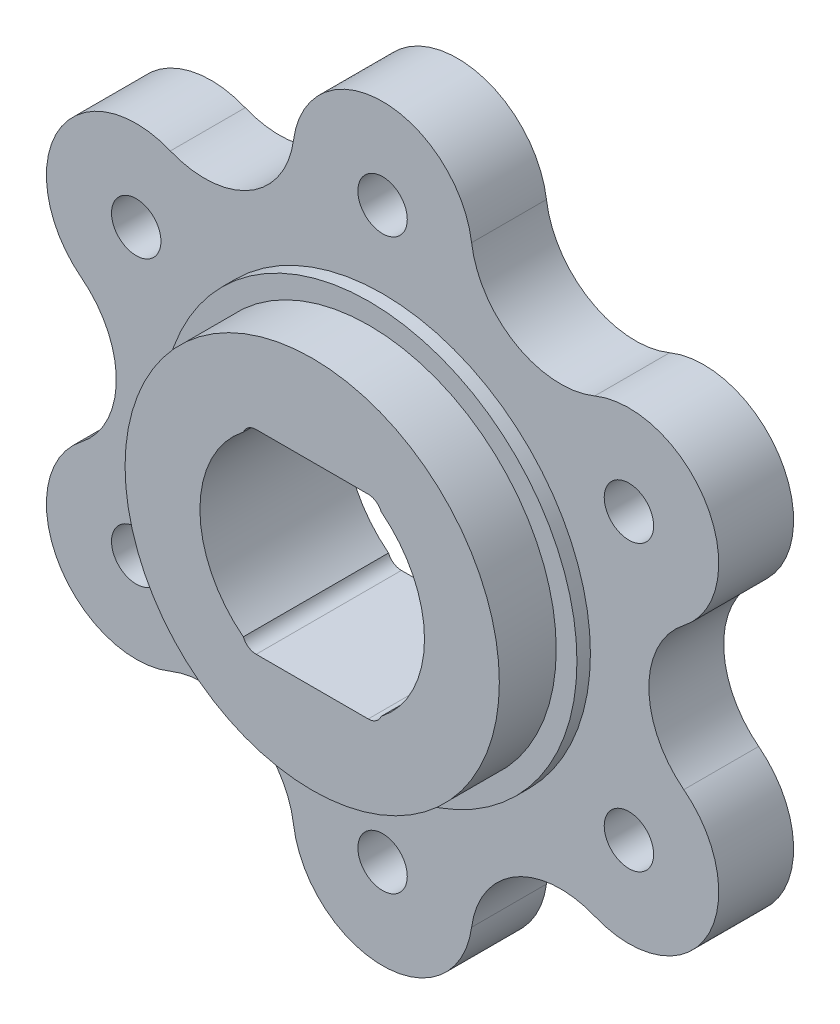
SolidWorks part; units mm, degrees
note: The reader was unsure of these and kept them because the rebuilt part matched: shared geometry of "ｽｹｯﾁ1<3>", "ｽｹｯﾁ1<4>", "ｽｹｯﾁ1<5>".
material "3.1325 (EN-AW 2017A)"
ref_plane "正面" through (0, 0, 0) normal (0, 0, 1) x (1, 0, 0)
ref_plane "平面" through (0, 0, 0) normal (0, 1, 0) x (1, 0, 0)
ref_plane "右側面" through (0, 0, 0) normal (1, 0, 0) x (0, 0, -1)
sketch "ｽｹｯﾁ1" plane through (0, 0, 0) normal (0, 0, 1) x (1, 0, 0)
  line L0 (-3.7417, 6.5) -> (3.7417, 6.5)
  line L1 (3.7417, -6.5) -> (-3.7417, -6.5)
  line L2 (0, 0) -> (0, 19) construction
  arc A0 (-3.7417, 6.5) -> (-3.7417, -6.5) centre (0, 0) ccw
  arc A1 (3.7417, -6.5) -> (3.7417, 6.5) centre (0, 0) ccw
  circle A2 centre (0, 0) radius 12.5
  circle A3 centre (0, 0) radius 13.883
  arc A4 (5.9465, 19.7996) -> (-5.9465, 19.7996) centre (0, 19) ccw
  arc A5 (5.9465, 19.7996) -> (14.1737, 15.0496) centre (11.893, 20.5992) ccw
  arc A6 (20.1202, 4.75) -> (14.1737, 15.0496) centre (16.4545, 9.5) ccw
  arc A7 (20.1202, 4.75) -> (20.1202, -4.75) centre (23.7859, 0) ccw
  arc A8 (14.1737, -15.0496) -> (20.1202, -4.75) centre (16.4545, -9.5) ccw
  arc A9 (14.1737, -15.0496) -> (5.9465, -19.7996) centre (11.893, -20.5992) ccw
  arc A10 (-5.9465, -19.7996) -> (5.9465, -19.7996) centre (0, -19) ccw
  arc A11 (-5.9465, -19.7996) -> (-14.1737, -15.0496) centre (-11.893, -20.5992) ccw
  arc A12 (-20.1202, -4.75) -> (-14.1737, -15.0496) centre (-16.4545, -9.5) ccw
  arc A13 (-20.1202, -4.75) -> (-20.1202, 4.75) centre (-23.7859, 0) ccw
  arc A14 (-14.1737, 15.0496) -> (-20.1202, 4.75) centre (-16.4545, 9.5) ccw
  arc A15 (-14.1737, 15.0496) -> (-5.9465, 19.7996) centre (-11.893, 20.5992) ccw
  circle A16 centre (0, 0) radius 19 construction
  circle A18 centre (0, 0) radius 4
  point P41 (0, 0)
  dimension "D1" = 15
  dimension "D3" = 25
  dimension "D4" = 27.766
  dimension "D5" = 6
  dimension "D6" = 6
  dimension "D7" = 6
  dimension "D8" = 38
  dimension "D9" = 8
  dimension "D2" = 13
extrude "ﾎﾞｽ - 押し出し1" add sketch "ｽｹｯﾁ1" along normal blind 5 contours A5 A6 A7 A8 A9 A10 A11 A12 A13 A14 A15 A4
extrude "ﾎﾞｽ - 押し出し2" add sketch "ｽｹｯﾁ1<3>" along normal blind 5.9 contours A3
sketch "ｽｹｯﾁ1<3>" plane through (0, 0, 0) normal (0, 0, 1) x (1, 0, 0) same geometry as "ｽｹｯﾁ1"
extrude "ﾎﾞｽ - 押し出し3" add sketch "ｽｹｯﾁ1<4>" along normal blind 9.7 contours A2
sketch "ｽｹｯﾁ1<4>" plane through (0, 0, 0) normal (0, 0, 1) x (1, 0, 0) same geometry as "ｽｹｯﾁ1"
extrude "ｶｯﾄ - 押し出し1" cut sketch "ｽｹｯﾁ1<5>" along normal through all contours L0 A1 L1 A0
sketch "ｽｹｯﾁ1<5>" plane through (0, 0, 0) normal (0, 0, 1) x (1, 0, 0) same geometry as "ｽｹｯﾁ1"
hole_wizard "M4x0.7 ねじ穴1" positions "3Dｽｹｯﾁ1" profile "ｽｹｯﾁ2" tap size "M4x0.7" standard "JIS" end condition through all
sketch3d "3Dｽｹｯﾁ1"
  point P0 (0, 19, 0)
  point P2 (16.4545, 9.5, 0)
  point P4 (16.4545, -9.5, 0)
  point P6 (0, -19, 0)
  point P8 (-16.4545, -9.5, 0)
  point P10 (-16.4545, 9.5, 0)
sketch "ｽｹｯﾁ2" plane through (0, 19, 0) normal (1, 0, 0) x (0, 1, 0)
  line L0 (0, 0) -> (0, 9.7)
  line L1 (0, 9.7) -> (1.65, 9.7)
  line L2 (1.65, 9.7) -> (1.65, 0)
  line L5 (1.65, 0) -> (0, 0)
  line L11 (0, -6.35) -> (0, 107.95) construction
  dimension "次ｻｰﾌｪｽまでのねじ下穴ﾄﾞﾘﾙ直径" = 3.3
  dimension "次ｻｰﾌｪｽまでのねじ下穴ﾄﾞﾘﾙの深さ" = 9.7
cosmetic thread "穴のねじ山1" parameters "D2"=4
cosmetic thread "穴のねじ山2" parameters "D2"=4
cosmetic thread "穴のねじ山3" parameters "D2"=4
cosmetic thread "穴のねじ山4" parameters "D2"=4
cosmetic thread "穴のねじ山5" parameters "D2"=4
cosmetic thread "穴のねじ山6" parameters "D2"=4
hole_wizard "M5 穴付きねじ用座ぐり穴1" [suppressed] positions "3Dｽｹｯﾁ2" profile "ｽｹｯﾁ3" counterbore size "M5" standard "JIS"
sketch3d "3Dｽｹｯﾁ2"
  point P0 (0, 0, 9.7)
sketch "ｽｹｯﾁ3" plane through (0, 0, 9.7) normal (1, 0, 0) x (0, -1, 0)
  line L0 (0, 0) -> (0, 9.7)
  line L1 (0, 9.7) -> (2.65, 9.7)
  line L3 (2.65, 9.7) -> (2.65, 5)
  line L4 (2.65, 5) -> (5, 5)
  line L5 (5, 5) -> (5, 0)
  line L7 (5, 0) -> (0, 0)
  line L11 (0, -6.35) -> (0, 107.95) construction
  dimension "通し穴の直径" = 5.3
  dimension "通し穴の深さ" = 9.7
  dimension "座ぐり穴の直径" = 10
  dimension "座ぐり穴の深さ" = 5
hole_wizard "M4 丸皿ねじ用皿穴1" [suppressed] positions "3Dｽｹｯﾁ3" profile "ｽｹｯﾁ4" countersink size "M4" standard "JIS"
sketch3d "3Dｽｹｯﾁ3"
  point P0 (0, 19, 5)
  point P2 (-16.4545, 9.5, 5)
  point P4 (-16.4545, -9.5, 5)
  point P6 (0, -19, 5)
  point P8 (16.4545, -9.5, 5)
  point P10 (16.4545, 9.5, 5)
sketch "ｽｹｯﾁ4" plane through (0, 19, 5) normal (1, 0, 0) x (0, -1, 0)
  line L0 (0, 0) -> (0, 5)
  line L1 (0, 5) -> (2.15, 5)
  line L2 (2.15, 5) -> (2.15, 2.55)
  line L3 (2.15, 2.55) -> (4.7, 0)
  line L5 (4.7, 0) -> (0, 0)
  line L6 (-2.15, 2.55) -> (-4.7, 0) construction
  line L11 (0, -6.35) -> (0, 107.95) construction
  dimension "通し穴の直径" = 4.3
  dimension "通し穴の深さ" = 5
  dimension "表面の皿穴の直径" = 9.4
  dimension "表面の皿穴の角度" = 90
sketch "ｽｹｯﾁ5" plane through (0, 0, 9.7) normal (0, 0, 1) x (1, 0, 0)
  line L0 (-3.7417, 6.5) -> (3.7417, 6.5) construction
  line L1 (1.8509, 0) -> (0, 0) construction
  line L2 (0, 0) -> (0, 10.209) construction
  circle A0 centre (3.7417, 5.5702) radius 0.9298
  circle A1 centre (3.7417, -5.5702) radius 0.9298
  circle A2 centre (-3.7417, -5.5702) radius 0.9298
  circle A3 centre (-3.7417, 5.5702) radius 0.9298
  dimension "D1" = 1.8596
extrude "ｶｯﾄ - 押し出し2" cut sketch "ｽｹｯﾁ5" against normal through all
